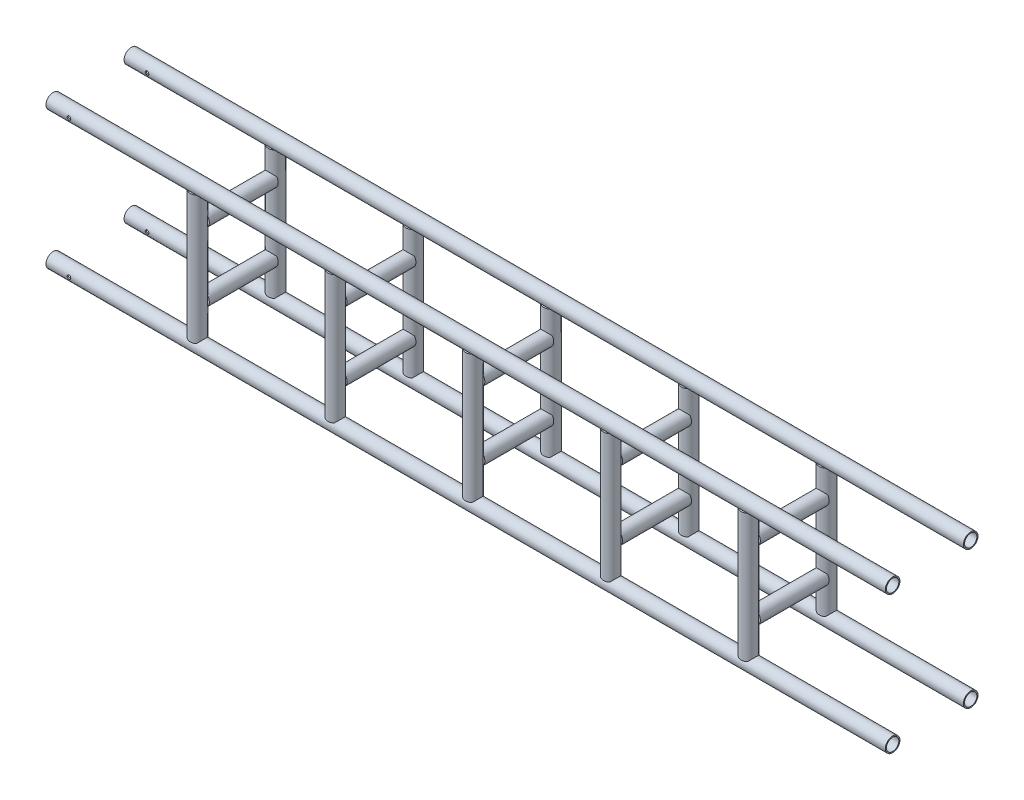
SolidWorks part; units mm, degrees
ref_plane "Front Plane" through (0, 0, 0) normal (0, 0, 1) x (1, 0, 0)
ref_plane "Top Plane" through (0, 0, 0) normal (0, 1, 0) x (1, 0, 0)
ref_plane "Right Plane" through (0, 0, 0) normal (1, 0, 0) x (0, 0, -1)
sketch "Sketch2" plane through (0, 0, 0) normal (1, 0, 0) x (0, 0, -1)
  line L0 (-85, 0) -> (-71.538, 0) construction
  line L1 (-71.538, 0) -> (-69.125, 0) construction
  line L2 (-69.125, 0) -> (69.125, 0) construction
  line L3 (69.125, 0) -> (71.538, 0) construction
  line L4 (71.538, 0) -> (85, 0) construction
  line L5 (-85, 0) -> (-85, 300) construction
  line L6 (-85, 300) -> (85, 300) construction
  line L7 (85, 300) -> (85, 0) construction
  line L8 (-85, 315.875) -> (85, 315.875) construction
  line L10 (-85, -15.875) -> (85, -15.875) construction
  circle A0 centre (-85, 0) radius 15.875
  circle A1 centre (-85, 0) radius 13.462
  circle A2 centre (85, 0) radius 13.462
  circle A3 centre (85, 0) radius 15.875
  circle A4 centre (-85, 300) radius 13.462
  circle A5 centre (-85, 300) radius 15.875
  circle A6 centre (85, 300) radius 13.462
  circle A7 centre (85, 300) radius 15.875
  dimension "D1" = 31.75
  dimension "D2" = 2.413
  dimension "D3" = 170
  dimension "D4" = 300
extrude "Boss-Extrude1" add sketch "Sketch2" along normal blind 914 and the other way blind 914
sketch "Sketch3" plane through (0, 0, 0) normal (0, 1, 0) x (1, 0, 0)
  line L0 (0, -85) -> (0, 85) construction
  line L1 (0, 85) -> (914, 85) construction
  line L2 (914, 85) -> (914, -85) construction
  line L3 (914, -85) -> (0, -85) construction
  line L4 (914, 69.125) -> (914, 100.875) construction
  circle A0 centre (0, 85) radius 15.875
  circle A1 centre (0, -85) radius 15.875
  circle A2 centre (300, -85) radius 15.875
  circle A3 centre (300, 85) radius 15.875
  circle A4 centre (600, -85) radius 15.875
  circle A5 centre (600, 85) radius 15.875
  circle A6 centre (-300, -85) radius 15.875
  circle A7 centre (-300, 85) radius 15.875
  circle A8 centre (-600, -85) radius 15.875
  circle A9 centre (-600, 85) radius 15.875
  dimension "D1" = 31.75
  dimension "D2" = 3
  dimension "D3" = 300
  dimension "D5" = 300
  dimension "D4" = 3
extrude "Boss-Extrude2" add sketch "Sketch3" along normal blind 280 from offset 10 contours A8 | A6 | A1 | A2 | A4 | A5 | A3 | A0 | A7 | A9
sketch "Sketch4" plane through (0, 0, 0) normal (0, 0, 1) x (1, 0, 0)
  line L0 (-300, 230) -> (-300, 80) construction
  line L1 (-600, 230) -> (600, 230) construction
  line L2 (-600, 230) -> (-600, 80) construction
  line L3 (-600, 80) -> (600, 80) construction
  line L4 (600, 230) -> (600, 80) construction
  line L5 (-600, 230) -> (600, 80) construction
  line L6 (-600, 80) -> (600, 230) construction
  line L7 (0, 155) -> (0, 0) construction
  line L8 (0, 230) -> (0, 80) construction
  line L10 (300, 230) -> (300, 80) construction
  circle A0 centre (-600, 230) radius 15.875
  circle A1 centre (-600, 80) radius 15.875
  circle A2 centre (0, 230) radius 15.875
  circle A3 centre (0, 80) radius 15.875
  circle A4 centre (600, 80) radius 15.875
  circle A5 centre (600, 230) radius 15.875
  circle A6 centre (-300, 230) radius 15.875
  circle A7 centre (-300, 80) radius 15.875
  circle A8 centre (300, 80) radius 15.875
  circle A9 centre (300, 230) radius 15.875
  point P0 (0, 155)
  dimension "D1" = 300
  dimension "D5" = 31.75
  dimension "D2" = 300
  dimension "D3" = 300
  dimension "D4" = 300
  dimension "D6" = 80
  dimension "D7" = 150
extrude "Boss-Extrude3" add sketch "Sketch4" along normal blind 75 and the other way blind 75
sketch "Sketch5" plane through (0, 0, 0) normal (0, 0, 1) x (1, 0, 0)
  line L0 (0, 0) -> (-914, 0) construction
  line L1 (-914, 15.875) -> (-914, -15.875) construction
  line L2 (-914, 0) -> (-914, 300) construction
  line L3 (-914, 315.875) -> (-914, 284.125) construction
  line L4 (-914, 300) -> (-864, 300) construction
  line L5 (-864, 300) -> (-864, 0) construction
  circle A0 centre (-864, 0) radius 4
  circle A1 centre (-864, 300) radius 4
  dimension "D3" = 8
  dimension "D1" = 50
  dimension "D2" = 300
extrude "Cut-Extrude1" cut sketch "Sketch5" against normal blind 200 and the other way blind 200
